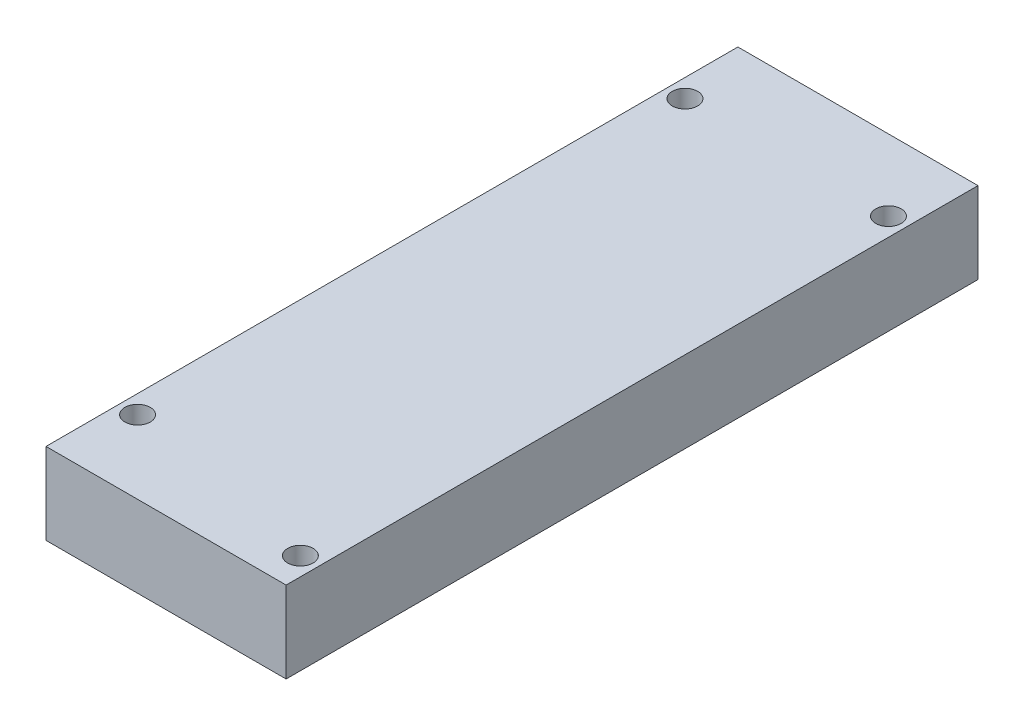
SolidWorks part; units mm, degrees
material "6061 Alloy"
ref_plane "Front Plane" through (0, 0, 0) normal (0, 0, 1) x (1, 0, 0)
ref_plane "Top Plane" through (0, 0, 0) normal (0, 1, 0) x (1, 0, 0)
ref_plane "Right Plane" through (0, 0, 0) normal (1, 0, 0) x (0, 0, -1)
sketch "Sketch1" plane through (0, 0, 0) normal (0, 0, 1) x (1, 0, 0)
  line L1 (-12.1622, 1.6878) -> (17.8098, 1.6878)
  line L2 (-12.1622, 1.6878) -> (-12.1622, -8.4722)
  line L3 (-12.1622, -8.4722) -> (17.8098, -8.4722)
  line L4 (17.8098, 1.6878) -> (17.8098, -8.4722)
  dimension "D1" = 29.972
  dimension "D2" = 10.16
extrude "Boss-Extrude1" add sketch "Sketch1" along normal blind 86.36
sketch "Sketch2" plane through (0, 1.6878, 0) normal (0, 1, 0) x (1, 0, 0)
  line L0 (17.8098, 0) -> (-12.1622, 0) construction
  line L1 (-12.1622, -86.36) -> (-12.1622, 0) construction
  line L2 (17.8098, -86.36) -> (17.8098, 0) construction
  line L4 (17.8098, -86.36) -> (-12.1622, -86.36) construction
  circle A0 centre (-9.8762, -8.89) radius 1.5875
  circle A1 centre (15.5238, -8.89) radius 1.5875
  circle A2 centre (-9.8762, -77.216) radius 1.5875
  circle A3 centre (15.5238, -82.296) radius 1.5875
  dimension "D1" = 3.175
  dimension "D2" = 8.89
  dimension "D3" = 2.286
  dimension "D4" = 2.286
  dimension "D5" = 9.144
  dimension "D6" = 4.064
extrude "Cut-Extrude1" cut sketch "Sketch2" against normal blind 12.7
ref_axis "Axis1" through (-9.8762, -8.4722, 8.89) along (0, 1, 0)
ref_axis "Axis2" through (15.5238, -8.4722, 8.89) along (0, 1, 0)
ref_axis "Axis3" through (15.5238, -8.4722, 82.296) along (0, 1, 0)
ref_axis "Axis4" through (-9.8762, -8.4722, 77.216) along (0, 1, 0)
